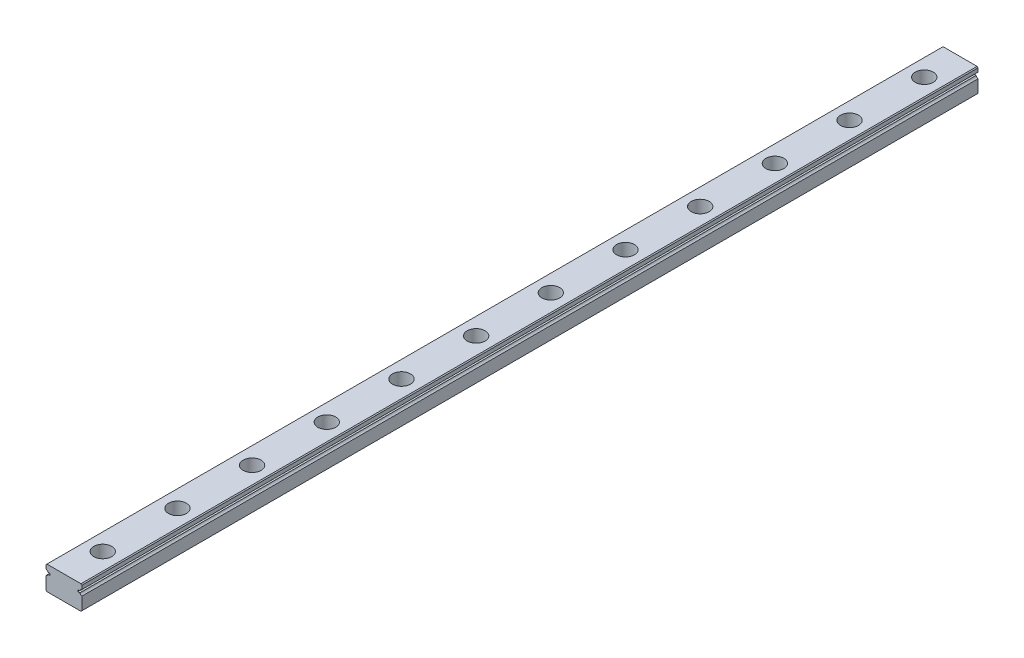
SolidWorks part; units mm, degrees
ref_plane "Спереди" through (0, 0, 0) normal (0, 0, 1) x (1, 0, 0)
ref_plane "Сверху" through (0, 0, 0) normal (0, 1, 0) x (1, 0, 0)
ref_plane "Справа" through (0, 0, 0) normal (1, 0, 0) x (0, 0, -1)
sketch "Эскиз1" plane through (0, 0, 0) normal (0, 0, 1) x (1, 0, 0)
  line L0 (-6, 3.7) -> (-5.7, 4)
  line L1 (-5.7, -4) -> (5.7, -4)
  line L2 (-6, -3.7) -> (-6, 0.549)
  line L3 (-5.7, 4) -> (5.7, 4)
  line L4 (6, -3.7) -> (6, 0.549)
  line L5 (-6, -4) -> (6, 4) construction
  line L6 (-6, 4) -> (6, -4) construction
  line L7 (-6, -3.7) -> (-5.7, -4)
  line L8 (5.7, -4) -> (6, -3.7)
  line L9 (5.7, 4) -> (6, 3.7)
  line L10 (-6, 2.451) -> (-6, 3.7)
  line L11 (-5.3546, 1.7981) -> (-4.6435, 1.7981)
  line L12 (0, 5.4188) -> (0, -5.747) construction
  line L13 (-5.3546, 1.2019) -> (-4.6435, 1.2019)
  line L14 (-4.6435, 1.7981) -> (-4.6435, 1.2019)
  line L15 (4.6435, 1.7981) -> (4.6435, 1.2019)
  line L16 (5.3546, 1.2019) -> (4.6435, 1.2019)
  line L17 (5.3546, 1.7981) -> (4.6435, 1.7981)
  line L18 (6, 2.451) -> (6, 3.7)
  line L19 (4.6435, 1.7981) -> (5.3546, 1.7981) construction
  arc A0 (-6, 0.549) -> (-5.3546, 1.2019) centre (-6.3091, 1.5) ccw
  arc A1 (-5.3546, 1.7981) -> (-6, 2.451) centre (-6.3091, 1.5) ccw
  arc A2 (5.3546, 1.7981) -> (6, 2.451) centre (6.3091, 1.5) cw
  arc A3 (6, 0.549) -> (5.3546, 1.2019) centre (6.3091, 1.5) cw
  point P0 (0, 0)
extrude "Бобышка-Вытянуть1" add sketch "Эскиз1" along normal blind 300
sketch "Эскиз2" plane through (0, 4, 0) normal (0, 1, 0) x (1, 0, 0)
  line L0 (0, 0) -> (0, -26.2396) construction
  line L1 (5.7, 0) -> (-5.7, 0) construction
  line L2 (-3.8306, -12) -> (3.8306, -12) construction
  circle A0 centre (0, -12) radius 3
  circle A1 centre (0, -12) radius 1.75
  dimension "D2" = 3.5
  dimension "D3" = 6
  dimension "D1" = 12
extrude "Вырез-Вытянуть1" cut sketch "Эскиз2" against normal blind 4.5
extrude "Вырез-Вытянуть2" cut sketch "Эскиз2<2>" against normal through all contours A1 region at (0, 4, 12)
sketch "Эскиз2<2>" plane through (0, 4, 0) normal (0, 1, 0) x (1, 0, 0) same geometry as "Эскиз2"
pattern_linear "Линейный массив1" count 14 spacing 25 along (0, 0, 1) of "Вырез-Вытянуть1", "Вырез-Вытянуть2"
